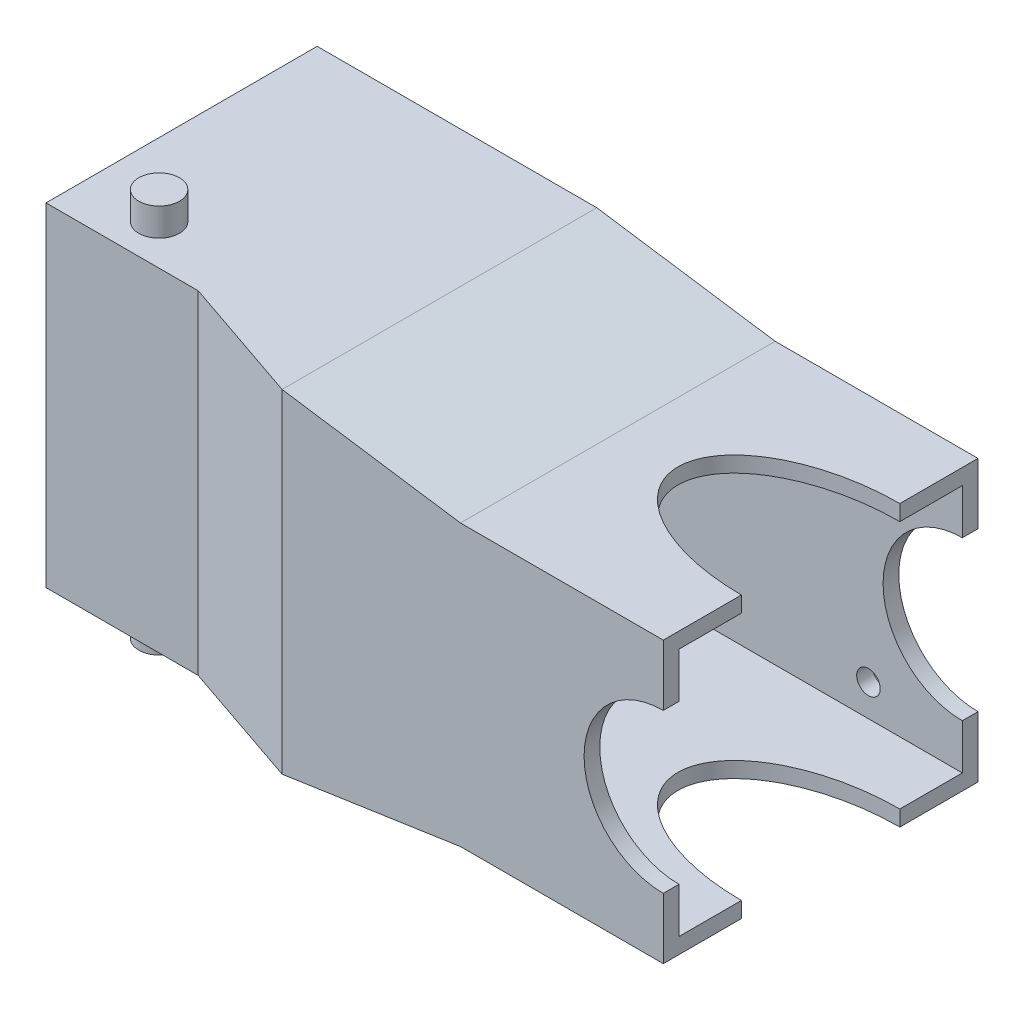
SolidWorks part; units mm, degrees
ref_plane "Plan de face" through (0, 0, 0) normal (0, 0, 1) x (1, 0, 0)
ref_plane "Plan de dessus" through (0, 0, 0) normal (0, 1, 0) x (1, 0, 0)
ref_plane "Plan de droite" through (0, 0, 0) normal (1, 0, 0) x (0, 0, -1)
sketch "Esquisse1" plane through (0, 0, 0) normal (1, 0, 0) x (0, 0, -1)
  line L1 (22.05, -19.635) -> (-22.05, -19.635)
  line L2 (22.05, -19.635) -> (22.05, 19.635)
  line L3 (22.05, 19.635) -> (-22.05, 19.635)
  line L4 (-22.05, -19.635) -> (-22.05, 19.635)
  line L5 (22.05, -19.635) -> (-22.05, 19.635) construction
  line L6 (22.05, 19.635) -> (-22.05, -19.635) construction
  point P0 (0, 0)
  dimension "D1" = 39.27
  dimension "D2" = 44.1
extrude "Boss.-Extru.1" add sketch "Esquisse1" along normal blind 28.42
sketch "Esquisse2" plane through (0, 0, 0) normal (-1, 0, 0) x (0, 0, 1)
  line L0 (22.05, 19.635) -> (22.05, -19.635) construction
  line L1 (-19.85, 17.435) -> (19.85, 17.435)
  line L2 (-19.85, 17.435) -> (-19.85, -17.435)
  line L3 (-19.85, -17.435) -> (19.85, -17.435)
  line L4 (19.85, 17.435) -> (19.85, -17.435)
  line L5 (-19.85, 17.435) -> (19.85, -17.435) construction
  line L6 (-19.85, -17.435) -> (19.85, 17.435) construction
  line L7 (-22.05, 19.635) -> (22.05, 19.635) construction
  point P0 (0, 0)
  dimension "D1" = 2.2
  dimension "D2" = 2.2
extrude "Enlèv. mat.-Extru.1" cut sketch "Esquisse2" against normal blind 28.42
sketch "Esquisse3" plane through (0, 0, 22.05) normal (0, 0, 1) x (1, 0, 0)
  line L0 (28.42, 19.635) -> (28.42, -19.635) construction
  circle A0 centre (28.42, 0) radius 11.1
extrude "Enlèv. mat.-Extru.2" cut sketch "Esquisse3" against normal blind 50
sketch "Esquisse4" plane through (0, -19.635, 0) normal (0, -1, 0) x (1, 0, 0)
  line L0 (28.42, 22.05) -> (28.42, -22.05) construction
  ellipse E0 centre (28.42, 0) end of major axis (8.42, 0) minor radius 11.1
extrude "Enlèv. mat.-Extru.3" cut sketch "Esquisse4" against normal blind 50
sketch "Esquisse5" plane through (0, 0, -22.05) normal (0, 0, -1) x (-1, 0, 0)
  line L0 (-28.42, -19.635) -> (-28.42, -11.1) construction
  line L2 (-28.42, -19.635) -> (0, -19.635) construction
  line L3 (0, 0) -> (-17.32, 0) construction
  circle A0 centre (-15.27, -12.985) radius 1.65
  arc A1 (-28.42, -11.1) -> (-28.42, 11.1) centre (-28.42, 0) ccw construction
  circle A2 centre (-15.27, 12.985) radius 1.65
  point P4 (-28.42, -15.3675)
  point P7 (-14.21, -19.635)
  dimension "D1" = 13.15
  dimension "D2" = 6.65
extrude "Enlèv. mat.-Extru.4" cut sketch "Esquisse5" against normal blind 10
sketch "Esquisse6" plane through (0, 0, -22.05) normal (0, 0, -1) x (-1, 0, 0)
  line L0 (0, 19.635) -> (0, -19.635)
  line L1 (0, 19.635) -> (64.18, 19.635)
  line L2 (0, -19.635) -> (64.18, -19.635)
  line L3 (64.18, 19.635) -> (64.18, -19.635)
  dimension "D1" = 64.18
extrude "Boss.-Extru.2" add sketch "Esquisse6" against normal blind 2.2
sketch "Esquisse7" plane through (0, 0, -22.05) normal (0, 0, -1) x (-1, 0, 0)
  line L0 (0, 0) -> (64.18, 0) construction
  line L1 (64.18, -19.635) -> (64.18, 19.635) construction
sketch "Esquisse8" plane through (0, 0, 0) normal (-1, 0, 0) x (0, 0, 1)
  line L0 (22.05, -19.635) -> (-22.05, -19.635)
  line L1 (22.05, -19.635) -> (22.05, 19.635)
  line L2 (-22.05, -19.635) -> (-22.05, 19.635)
  line L3 (22.05, 19.635) -> (-22.05, 19.635)
extrude "Boss.-Extru.3" add sketch "Esquisse8" along normal blind 25
sketch "Esquisse10" plane through (0, 0, 22.05) normal (0, 0, 1) x (1, 0, 0)
  line L0 (-25, -19.635) -> (0, -19.635)
  line L1 (28.42, -19.635) -> (-25, -19.635) construction
  line L2 (0, -19.635) -> (-25, -23.345)
  line L3 (-25, -23.345) -> (-25, -19.635)
  line L4 (-25, 0) -> (0, 0) construction
  line L5 (-25, -19.635) -> (-25, 19.635) construction
  line L6 (-25, 19.635) -> (0, 19.635)
  line L7 (-25, 23.345) -> (-25, 19.635)
  line L8 (0, 19.635) -> (-25, 23.345)
  dimension "D1" = 3.71
extrude "Boss.-Extru.4" add sketch "Esquisse10" against normal up to vertex (44.1 mm away) up to point (28.42, -19.635, -22.05)
sketch "Esquisse13" plane through (0, 0, -22.05) normal (0, 0, -1) x (-1, 0, 0)
  line L0 (64.18, 19.635) -> (25, 19.635)
  line L1 (64.18, 19.635) -> (64.18, 23.345)
  line L2 (25, 19.635) -> (25, 23.345)
  line L3 (64.18, 23.345) -> (25, 23.345)
  line L4 (25, -23.345) -> (25, -19.635)
  line L5 (25, -23.345) -> (64.18, -23.345)
  line L6 (25, -19.635) -> (64.18, -19.635)
  line L7 (64.18, -23.345) -> (64.18, -19.635)
extrude "Boss.-Extru.5" add sketch "Esquisse13" against normal up to vertex (2.2 mm away) up to point (-25, 19.635, -19.85)
sketch "Esquisse14" plane through (0, 0, 0) normal (1, 0, 0) x (0, 0, -1)
  line L0 (-19.85, 17.435) -> (19.85, 17.435)
  line L1 (-19.85, 17.435) -> (-19.85, -17.435)
  line L2 (19.85, 17.435) -> (19.85, -17.435)
  line L3 (-19.85, -17.435) -> (19.85, -17.435)
extrude "Enlèv. mat.-Extru.5" cut sketch "Esquisse14" against normal blind 25
sketch "Esquisse17" plane through (-64.18, 0, 0) normal (-1, 0, 0) x (0, 0, 1)
  line L0 (-22.05, 23.345) -> (-22.05, -23.345)
  line L1 (-22.05, 23.345) -> (15.95, 23.345)
  line L2 (-22.05, -23.345) -> (15.95, -23.345)
  line L3 (15.95, 23.345) -> (15.95, -23.345)
  dimension "D1" = 46.69
  dimension "D2" = 38
extrude "Boss.-Extru.6" add sketch "Esquisse17" against normal up to vertex (39.18 mm away) up to point (-25, 23.345, 22.05)
sketch "Esquisse18" plane through (-64.18, 0, 0) normal (-1, 0, 0) x (0, 0, 1)
  line L0 (-21.4975, 21.145) -> (13.75, 21.145)
  line L1 (-21.4975, 21.145) -> (-21.4975, -21.145)
  line L2 (13.75, 21.145) -> (13.75, -21.145)
  line L3 (-21.4975, -21.145) -> (13.75, -21.145)
  line L4 (15.95, 23.345) -> (-22.05, 23.345) construction
  line L5 (15.95, -23.345) -> (-22.05, -23.345) construction
  line L6 (15.95, -23.345) -> (15.95, 23.345) construction
  point P6 (-3.8738, 21.145)
  point P9 (13.75, 0)
  dimension "D1" = 2.2
  dimension "D2" = 2.2
  dimension "D3" = 2.2
extrude "Enlèv. mat.-Extru.6" cut sketch "Esquisse18" against normal blind 50
ref_plane "Plan7" through (-25, -17.435, 15.95) normal (0, 1, 0) x (1, 0, 0)
sketch "Esquisse21" plane through (0, 0, 22.05) normal (0, 0, 1) x (1, 0, 0)
sketch "Esquisse22" plane through (0, -23.345, 0) normal (0, -1, 0) x (1, 0, 0)
  line L0 (-42.8457, 15.95) -> (-25, 15.95)
  line L1 (-25, 15.95) -> (-25, 22.05)
  line L2 (-25, 22.05) -> (-42.8457, 15.95)
extrude "Boss.-Extru.7" add sketch "Esquisse22" against normal up to vertex (46.69 mm away) up to point (-25, 23.345, 15.95)
fillet "Congé1" radius 50 1 edges at (-25, 0, 13.75)
sketch "Esquisse23" plane through (0, 23.345, 0) normal (0, 1, 0) x (1, 0, 0)
  line L0 (-64.18, -15.95) -> (-64.18, 22.05) construction
  line L1 (-42.8457, -15.95) -> (-64.18, -15.95) construction
  circle A0 centre (-53.98, -10.3) radius 2.85
  dimension "D1" = 10.2
  dimension "D2" = 5.65
extrude "Boss.-Extru.8" add sketch "Esquisse23" along normal blind 3.9
sketch "Esquisse24" plane through (0, 0, 15.95) normal (0, 0, 1) x (1, 0, 0)
  line L0 (-64.18, 0) -> (-42.8457, 0) construction
  line L1 (-64.18, -23.345) -> (-64.18, 23.345) construction
  line L2 (-42.8457, 23.345) -> (-42.8457, -23.345) construction
sketch "Esquisse26" plane through (0, -23.345, 0) normal (0, -1, 0) x (1, 0, 0)
  line L0 (-42.8457, 15.95) -> (-64.18, 15.95) construction
  line L1 (-64.18, 15.95) -> (-64.18, -22.05) construction
  circle A0 centre (-53.98, 10.3) radius 2.85
  dimension "D1" = 5.65
  dimension "D2" = 10.2
extrude "Boss.-Extru.9" add sketch "Esquisse26" along normal blind 3.9
equation "\"2.27.00mm\"=10"
